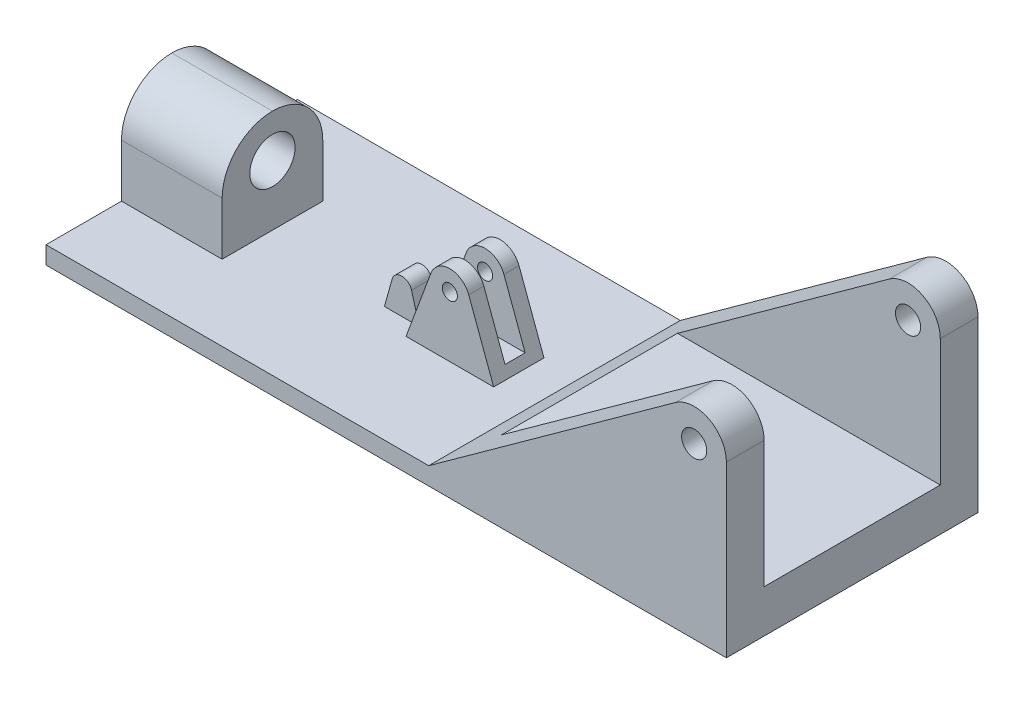
SolidWorks part; units mm, degrees
ref_plane "Plane1" through (0, 0, 0) normal (0, 0, 1) x (1, 0, 0)
ref_plane "Plane2" through (0, 0, 0) normal (0, 1, 0) x (1, 0, 0)
ref_plane "Plane3" through (0, 0, 0) normal (1, 0, 0) x (0, 0, -1)
other "Configuration Table"
sketch "Sketch1" plane through (0, 0, 0) normal (0, 0, 1) x (1, 0, 0)
  line L0 (-145.4421, 25.4143) -> (26.2619, 25.4143)
  line L1 (-145.4421, 29.8593) -> (26.2619, 29.8593)
  line L2 (26.2619, 29.8593) -> (26.2619, 25.4143)
  line L5 (-145.4421, 29.8593) -> (-145.4421, 25.4143)
  dimension "D1" = 171.704
  dimension "D2" = 4.445
extrude "Base-Extrude" add sketch "Sketch1" along normal mid plane 63.5
sketch "Sketch4" plane through (0, 0, 0) normal (0, 0, 1) x (1, 0, 0)
  line L0 (-145.4421, 25.4143) -> (-120.0421, 25.4143)
  line L1 (-145.4421, 25.4143) -> (26.2619, 25.4143) construction
  line L2 (-145.4421, 29.8593) -> (-145.4421, 25.4143) construction
  line L3 (-145.4421, 55.8943) -> (-120.0421, 55.8943)
  line L5 (-145.4421, 55.8943) -> (-145.4421, 25.4143)
  line L6 (-120.0421, 55.8943) -> (-120.0421, 25.4143)
  dimension "D1" = 30.48
  dimension "D2" = 25.4
extrude "Boss-Extrude3" add sketch "Sketch4" along normal mid plane 25.4
sketch "Sketch5" plane through (-120.0421, 0, 0) normal (1, 0, 0) x (0, 0, -1)
  circle A0 centre (0, 45.0963) radius 5.715 construction
  circle A1 centre (0, 45.0963) radius 5.715
extrude "Cut-Extrude1" cut sketch "Sketch5" against normal through all
sketch "Sketch3" plane through (0, 0, 0) normal (0, 0, 1) x (1, 0, 0)
  line L0 (-81.6272, 25.4143) -> (-56.2272, 25.4143)
  line L1 (-145.4421, 25.4143) -> (26.2619, 25.4143) construction
  line L8 (-64.1629, 46.8593) -> (-56.2272, 25.4143)
  line L9 (-68.9272, 45.0963) -> (-68.9272, -16.7892) construction
  line L10 (-73.6914, 46.8593) -> (-81.6272, 25.4143)
  circle A2 centre (-68.9272, 45.0963) radius 1.905
  arc A5 (-64.1629, 46.8593) -> (-73.6914, 46.8593) centre (-68.9272, 45.0963) ccw
  circle A6 centre (-68.9272, 45.0963) radius 1.905 construction
  dimension "D2" = 5.08
  dimension "D1" = 25.4
  dimension "D3" = 19.6819
  dimension "D4" = 95.189
sketch "Sketch2" plane through (0, 0, 0) normal (0, 0, 1) x (1, 0, 0)
  line L0 (-55.0181, 25.4143) -> (26.2619, 25.4143)
  line L2 (-145.4421, 25.4143) -> (26.2619, 25.4143) construction
  line L4 (26.2619, 68.1879) -> (26.2619, 25.4143)
  line L5 (26.2619, 29.8593) -> (26.2619, 25.4143) construction
  line L7 (13.377, 74.7786) -> (-55.0181, 25.4143)
  circle A2 centre (18.1339, 68.1879) radius 3.175 construction
  circle A3 centre (18.1339, 68.1879) radius 3.175
  arc A4 (26.2619, 68.1879) -> (13.377, 74.7786) centre (18.1339, 68.1879) ccw
  dimension "D2" = 8.128
  dimension "D1" = 81.28
  dimension "D3" = 42.7736
extrude "Boss-Extrude1" add sketch "Sketch3" along normal mid plane 12.7
extrude "Boss-Extrude2" add sketch "Sketch2" along normal mid plane 63.5
fillet "Fillet1" radius 12.7 4 edges at (-132.7421, 55.8943, 12.7) (-120.0421, 55.8943, 0) (-145.4421, 55.8943, 0) (-132.7421, 55.8943, -12.7)
sketch "Sketch6" plane through (0, 0, 0) normal (0, 0, 1) x (1, 0, 0)
  line L0 (-79.0424, 32.3993) -> (-58.812, 32.3993)
  line L1 (-79.9823, 29.8593) -> (-57.8721, 29.8593) construction
  line L3 (-73.6914, 46.8593) -> (-79.9823, 29.8593)
  line L4 (-79.9823, 29.8593) -> (-57.8721, 29.8593)
  line L5 (-57.8721, 29.8593) -> (-64.1629, 46.8593)
  line L6 (-73.6914, 46.8593) -> (-79.0424, 32.3993)
  line L8 (-58.812, 32.3993) -> (-64.1629, 46.8593)
  arc A1 (-64.1629, 46.8593) -> (-73.6914, 46.8593) centre (-68.9272, 45.0963) ccw
  arc A2 (-64.1629, 46.8593) -> (-73.6914, 46.8593) centre (-68.9272, 45.0963) ccw
  dimension "D2" = 2.54
  dimension "D1" = 0
extrude "Cut-Extrude2" cut sketch "Sketch6" against normal mid plane 5.08
sketch "Sketch7" plane through (0, 0, 0) normal (0, 0, 1) x (1, 0, 0)
  line L0 (13.377, 74.7786) -> (-48.8595, 29.8593) construction
  line L1 (26.2619, 68.1879) -> (26.2619, 25.4143) construction
  line L2 (13.377, 74.7786) -> (-40.0615, 36.2093)
  line L3 (26.2619, 68.1879) -> (26.2619, 36.2093)
  line L5 (-145.4421, 29.8593) -> (-48.8595, 29.8593) construction
  line L6 (-40.0615, 36.2093) -> (26.2619, 36.2093)
  arc A0 (26.2619, 68.1879) -> (13.377, 74.7786) centre (18.1339, 68.1879) ccw construction
  arc A1 (26.2619, 68.1879) -> (13.377, 74.7786) centre (18.1339, 68.1879) ccw
  dimension "D1" = 6.35
extrude "Cut-Extrude4" cut sketch "Sketch7" against normal mid plane 44.45
sketch "Sketch8" plane through (0, 0, 0) normal (0, 0, 1) x (1, 0, 0)
  line L0 (-90.4841, 25.4143) -> (-79.2219, 25.4143)
  line L1 (-145.4421, 25.4143) -> (26.2619, 25.4143) construction
  line L2 (-79.2219, 25.4143) -> (-82.4062, 36.8404)
  line L3 (-87.2997, 36.8404) -> (-90.4841, 25.4143)
  arc A0 (-82.4062, 36.8404) -> (-87.2997, 36.8404) centre (-84.853, 36.1585) ccw
  circle A1 centre (-68.9272, 45.0963) radius 1.905 construction
  dimension "D1" = 2.54
  dimension "D3" = 15.9258
  dimension "D2" = 10.7442
extrude "Boss-Extrude4" add sketch "Sketch8" along normal mid plane 5.08
